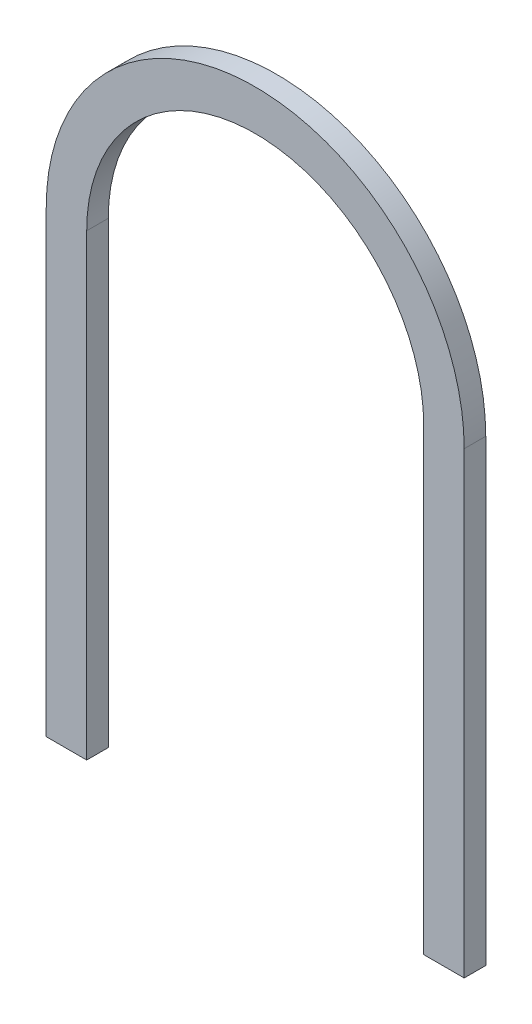
SolidWorks part; units mm, degrees
material "AISI 304"
ref_plane "Front Plane" through (0, 0, 0) normal (0, 0, 1) x (1, 0, 0)
ref_plane "Top Plane" through (0, 0, 0) normal (0, 1, 0) x (1, 0, 0)
ref_plane "Right Plane" through (0, 0, 0) normal (1, 0, 0) x (0, 0, -1)
sketch "Sketch1" plane through (0, 0, 0) normal (0, 0, 1) x (1, 0, 0)
  line L0 (-75, 80) -> (75, -80) construction
  line L1 (-75, 80) -> (75, 80)
  line L2 (-75, 80) -> (-75, -80)
  line L3 (-75, -80) -> (75, -80)
  line L4 (75, 80) -> (75, -80)
  point P0 (0, 0)
  point P6 (0, 0)
  dimension "D1" = 150
  dimension "D2" = 160
extrude "Boss-Extrude1" add sketch "Sketch1" along normal blind 3.2
sketch "Sketch2" plane through (0, 0, 3.2) normal (0, 0, 1) x (1, 0, 0)
  line L0 (0, -12) -> (0, -47.5) construction
  line L1 (-25, -12) -> (-25, -80)
  line L2 (25, -12) -> (25, -80)
  line L3 (-75, -80) -> (75, -80) construction
  line L4 (-25, -80) -> (25, -80)
  arc A1 (-25, -12) -> (25, -12) centre (0, -12) cw
  dimension "D1" = 35.5
  dimension "D3" = 25
  dimension "D4" = 68
extrude "Cut-Extrude1" cut sketch "Sketch2" against normal up to next
sketch "Sketch3" plane through (0, 0, 3.2) normal (0, 0, 1) x (1, 0, 0)
  line L0 (-31, -12) -> (-31, -80)
  line L1 (-75, -80) -> (-25, -80) construction
  line L2 (-31, -80) -> (-75, -80)
  line L3 (-75, -80) -> (-75, 80)
  line L4 (-75, 80) -> (75, 80)
  line L6 (75, 80) -> (75, -80)
  line L7 (25, -80) -> (75, -80) construction
  line L8 (31, -80) -> (31, -12)
  line L9 (75, -80) -> (31, -80)
  arc A4 (31, -12) -> (-31, -12) centre (0, -12) ccw
  dimension "D1" = 31
extrude "Cut-Extrude2" cut sketch "Sketch3" against normal up to next
